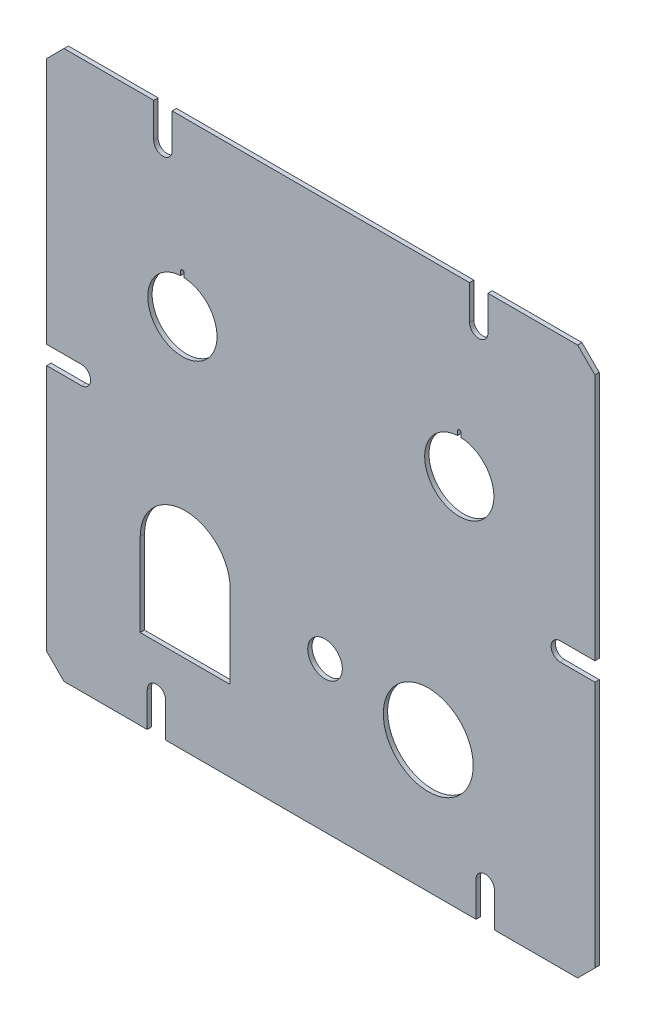
SolidWorks part; units mm, degrees
material "PE High Density"
ref_plane "Front" through (0, 0, 0) normal (0, 0, 1) x (1, 0, 0)
ref_plane "Top" through (0, 0, 0) normal (0, 1, 0) x (1, 0, 0)
ref_plane "Right" through (0, 0, 0) normal (1, 0, 0) x (0, 0, -1)
ref_axis "Axis1" through (0, 0, 55) along (0, 0, -1)
sketch "Sketch1" plane through (0, 0, 0) normal (0, 0, 1) x (1, 0, 0)
  line L1 (-100.584, 100.584) -> (100.584, 100.584)
  line L2 (-100.584, 100.584) -> (-100.584, -100.584)
  line L3 (-100.584, -100.584) -> (100.584, -100.584)
  line L4 (100.584, 100.584) -> (100.584, -100.584)
  line L5 (-100.584, 100.584) -> (100.584, -100.584) construction
  line L6 (-100.584, -100.584) -> (100.584, 100.584) construction
  point P0 (0, 0)
  dimension "D1" = 201.168
extrude "Boss-Extrude1" add sketch "Sketch1" along normal blind 1.5875
sketch "Sketch2" plane through (0, 0, 1.5875) normal (0, 0, 1) x (1, 0, 0)
  line L0 (100.584, -100.584) -> (100.584, 100.584) construction
  line L1 (100.584, 100.584) -> (-100.584, 100.584) construction
  circle A0 centre (-49.784, -40.5765) radius 16.5
  circle A1 centre (39.4206, -52.284) radius 16.5
  dimension "D1" = 33
  dimension "D2" = 61.1634
  dimension "D3" = 150.368
  dimension "D4" = 141.1605
  dimension "D5" = 152.868
extrude "Cut-Extrude1" cut sketch "Sketch2" against normal up to next
hole_wizard "1/4 Clearance Hole1" positions "Sketch3" profile "Sketch4" hole size "1/4" standard "ANSI Inch" end condition up to next
sketch "Sketch3" plane through (0, 0, 1.5875) normal (0, 0, 1) x (1, 0, 0)
  line L0 (0, 100.584) -> (0, -100.584) construction
  line L1 (100.584, 100.584) -> (-100.584, 100.584) construction
  line L2 (-100.584, -100.584) -> (100.584, -100.584) construction
  line L4 (-100.584, 0) -> (100.584, 0) construction
  line L5 (-100.584, 100.584) -> (-100.584, -100.584) construction
  line L6 (100.584, -100.584) -> (100.584, 100.584) construction
  line L8 (-57.9437, 87.884) -> (57.9438, 87.884) construction
  line L10 (-60.325, -87.884) -> (60.325, -87.884) construction
  point P0 (-57.9437, 87.884)
  point P2 (57.9438, 87.884)
  point P4 (87.884, 0)
  point P6 (-87.884, 0)
  point P8 (-60.325, -87.884)
  point P10 (60.325, -87.884)
  dimension "D1" = 12.7
  dimension "D2" = 115.8875
  dimension "D3" = 12.7
  dimension "D4" = 120.65
  dimension "D5" = 12.7
sketch "Sketch4" plane through (-57.9437, 87.884, 1.5875) normal (1, 0, 0) x (0, -1, 0)
  line L0 (0, 0) -> (0, 1.5875)
  line L1 (0, 1.5875) -> (3.3782, 1.5875)
  line L2 (3.3782, 1.5875) -> (3.3782, 0)
  line L5 (3.3782, 0) -> (0, 0)
  line L11 (0, -6.35) -> (0, 107.95) construction
  dimension "Thru Hole Dia." = 6.7564
  dimension "Thru Hole Depth" = 1.5875
chamfer "Chamfer1" distance 6.35 angle 45 4 edges at (-100.584, -100.584, 0.7937) (100.584, -100.584, 0.7937) (100.584, 100.584, 0.7937) (-100.584, 100.584, 0.7937)
sketch "Sketch5" plane through (0, 0, 0) normal (0, 0, -1) x (-1, 0, 0)
  line L0 (33.284, -40.5765) -> (33.284, -71.0565)
  line L1 (33.284, -71.0565) -> (66.284, -71.0565)
  line L2 (66.284, -71.0565) -> (66.284, -40.5765)
  circle A0 centre (49.784, -40.5765) radius 16.5 construction
  arc A1 (33.284, -40.5765) -> (66.284, -40.5765) centre (49.784, -40.5765) ccw
  dimension "D1" = 30.48
extrude "Cut-Extrude3" cut sketch "Sketch5" against normal up to next
sketch "Sketch6" plane through (0, 0, 0) normal (0, 0, -1) x (-1, 0, 0)
  line L0 (-50.8, 37.084) -> (50.8, 37.084) construction
  line L1 (0, 100.584) -> (0, -100.584) construction
  line L2 (-94.234, 100.584) -> (94.234, 100.584) construction
  line L3 (94.234, -100.584) -> (-94.234, -100.584) construction
  line L4 (-50.8, 37.084) -> (-50.8, 51.308) construction
  line L5 (50.8, 37.084) -> (50.8, 51.308) construction
  line L6 (-50.8, 51.308) -> (50.8, 51.308) construction
  line L7 (-50.165, 49.7681) -> (-50.165, 51.308)
  line L8 (51.435, 49.7681) -> (51.435, 51.308)
  line L9 (-51.435, 49.7681) -> (-51.435, 51.308)
  line L10 (50.165, 49.7681) -> (50.165, 51.308)
  line L11 (-51.435, 37.084) -> (-51.435, 51.308) construction
  line L12 (-50.165, 37.084) -> (-50.165, 51.308) construction
  line L13 (50.165, 37.084) -> (50.165, 51.308) construction
  line L14 (51.435, 37.084) -> (51.435, 51.308) construction
  arc A0 (-51.435, 49.7681) -> (-50.165, 49.7681) centre (-50.8, 37.084) ccw
  arc A1 (50.165, 49.7681) -> (51.435, 49.7681) centre (50.8, 37.084) ccw
  arc A2 (-51.435, 51.308) -> (-50.165, 51.308) centre (-50.8, 51.308) cw
  arc A3 (50.165, 51.308) -> (51.435, 51.308) centre (50.8, 51.308) cw
  dimension "D2" = 25.4
  dimension "D1" = 101.6
  dimension "D3" = 63.5
  dimension "D4" = 0.635
  dimension "D6" = 14.224
  dimension "D5" = 0.635
extrude "Cut-Extrude4" cut sketch "Sketch6" against normal up to next
sketch "Sketch7" plane through (0, 0, 0) normal (0, 0, -1) x (-1, 0, 0)
  line L0 (-61.322, 87.884) -> (-54.5656, 87.884) construction
  line L1 (54.5655, 87.884) -> (61.3219, 87.884) construction
  line L2 (-87.884, 3.3782) -> (-87.884, -3.3782) construction
  line L3 (87.884, 3.3782) -> (87.884, -3.3782) construction
  line L4 (-63.7032, -87.884) -> (-56.9468, -87.884) construction
  line L5 (56.9468, -87.884) -> (63.7032, -87.884) construction
  line L7 (-61.322, 87.884) -> (-54.5656, 87.884)
  line L8 (-61.322, 87.884) -> (-61.322, 102.362)
  line L9 (-61.322, 102.362) -> (-54.5656, 102.362)
  line L10 (-54.5656, 87.884) -> (-54.5656, 102.362)
  line L11 (-61.322, 87.884) -> (-54.5656, 102.362) construction
  line L12 (-61.322, 102.362) -> (-54.5656, 87.884) construction
  line L13 (54.5655, 87.884) -> (61.3219, 87.884)
  line L14 (54.5655, 87.884) -> (54.5655, 102.362)
  line L15 (54.5655, 102.362) -> (61.3219, 102.362)
  line L16 (61.3219, 87.884) -> (61.3219, 102.362)
  line L17 (54.5655, 87.884) -> (61.3219, 102.362) construction
  line L18 (54.5655, 102.362) -> (61.3219, 87.884) construction
  line L19 (87.884, 3.3782) -> (102.362, 3.3782)
  line L20 (87.884, 3.3782) -> (87.884, -3.3782)
  line L21 (87.884, -3.3782) -> (102.362, -3.3782)
  line L22 (102.362, 3.3782) -> (102.362, -3.3782)
  line L23 (87.884, 3.3782) -> (102.362, -3.3782) construction
  line L24 (87.884, -3.3782) -> (102.362, 3.3782) construction
  line L25 (56.9468, -87.884) -> (63.7032, -87.884)
  line L26 (56.9468, -87.884) -> (56.9468, -102.362)
  line L27 (56.9468, -102.362) -> (63.7032, -102.362)
  line L28 (63.7032, -87.884) -> (63.7032, -102.362)
  line L29 (56.9468, -87.884) -> (63.7032, -102.362) construction
  line L30 (56.9468, -102.362) -> (63.7032, -87.884) construction
  line L31 (-63.7032, -87.884) -> (-56.9468, -87.884)
  line L32 (-63.7032, -87.884) -> (-63.7032, -102.362)
  line L33 (-63.7032, -102.362) -> (-56.9468, -102.362)
  line L34 (-56.9468, -87.884) -> (-56.9468, -102.362)
  line L35 (-63.7032, -87.884) -> (-56.9468, -102.362) construction
  line L36 (-63.7032, -102.362) -> (-56.9468, -87.884) construction
  line L37 (-87.884, -3.3782) -> (-102.362, -3.3782)
  line L38 (-87.884, -3.3782) -> (-87.884, 3.3782)
  line L39 (-87.884, 3.3782) -> (-102.362, 3.3782)
  line L40 (-102.362, -3.3782) -> (-102.362, 3.3782)
  line L41 (-87.884, -3.3782) -> (-102.362, 3.3782) construction
  line L42 (-87.884, 3.3782) -> (-102.362, -3.3782) construction
  circle A0 centre (-57.9438, 87.884) radius 3.3782 construction
  circle A1 centre (57.9437, 87.884) radius 3.3782 construction
  circle A2 centre (-87.884, 0) radius 3.3782 construction
  circle A3 centre (87.884, 0) radius 3.3782 construction
  circle A4 centre (-60.325, -87.884) radius 3.3782 construction
  circle A5 centre (60.325, -87.884) radius 3.3782 construction
  point P1 (0, 0)
  point P6 (0, 0)
  point P16 (0, 0)
  point P21 (0, 0)
  point P26 (0, 0)
  point P33 (-57.9438, 95.123)
  point P37 (57.9437, 95.123)
  point P41 (95.123, 0)
  point P45 (60.325, -95.123)
  point P49 (-60.325, -95.123)
  point P53 (-95.123, 0)
  point P54 (0, 0)
  dimension "D1" = 14.478
extrude "Cut-Extrude5" cut sketch "Sketch7" against normal up to next
sketch "Sketch8" plane through (0, 0, 0) normal (0, 0, -1) x (-1, 0, 0)
  line L0 (100.584, -3.3782) -> (100.584, -94.234) construction
  line L1 (94.234, -100.584) -> (63.7032, -100.584) construction
  circle A0 centre (-1.5331, -45.5351) radius 6.35
  dimension "D1" = 12.7
  dimension "D2" = 102.1171
  dimension "D3" = 55.0489
extrude "PORT FOR POWER PLUG" cut sketch "Sketch8" against normal up to next
